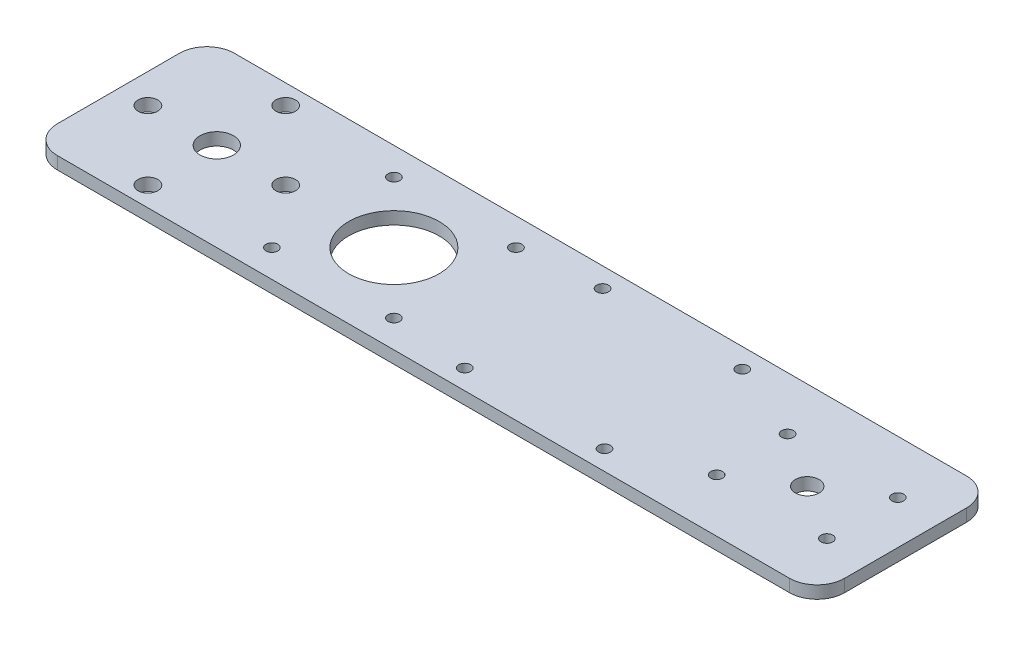
SolidWorks part; units mm, degrees
ref_plane "Front Plane" through (0, 0, 0) normal (0, 0, 1) x (1, 0, 0)
ref_plane "Top Plane" through (0, 0, 0) normal (0, 1, 0) x (1, 0, 0)
ref_plane "Right Plane" through (0, 0, 0) normal (1, 0, 0) x (0, 0, -1)
sketch "Sketch1" plane through (0, 0, 0) normal (0, 1, 0) x (1, 0, 0)
  line L0 (-25, 0) -> (0, 0) construction
  line L1 (-25, 22.5) -> (175, 22.5)
  line L2 (-25, 22.5) -> (-25, -22.5)
  line L3 (-25, -22.5) -> (175, -22.5)
  line L4 (175, 22.5) -> (175, -22.5)
  dimension "D1" = 25
  dimension "D2" = 200
  dimension "D3" = 45
extrude "Boss-Extrude1" add sketch "Sketch1" along normal blind 3.175
sketch "Sketch4" plane through (0, 3.175, 0) normal (0, 1, 0) x (1, 0, 0)
  line L0 (175, 0) -> (-25, 0) construction
  line L1 (175, -22.5) -> (175, 22.5) construction
  line L2 (-25, 22.5) -> (-25, -22.5) construction
  line L3 (150, 22.5) -> (150, -22.5) construction
  line L4 (175, 22.5) -> (-25, 22.5) construction
  line L5 (-25, -22.5) -> (175, -22.5) construction
  circle A0 centre (150, 0) radius 3
  circle A1 centre (136, 9) radius 1.5
  circle A2 centre (164, 9) radius 1.5
  circle A3 centre (164, -9) radius 1.5
  circle A4 centre (136, -9) radius 1.5
  point P8 (0, 0)
  point P14 (0, 0)
  point P15 (0, 0)
  point P16 (150, 27.4454)
  point P24 (0, 0)
  point P29 (0, 0)
  dimension "D1" = 6
  dimension "D5" = 3
  dimension "D2" = 25
  dimension "D3" = 14
  dimension "D4" = 9
extrude "Cut-Extrude1" cut sketch "Sketch4" against normal through all
sketch "Sketch5" plane through (0, 3.175, 0) normal (0, 1, 0) x (1, 0, 0)
  circle A0 centre (0, 0) radius 4.25
  dimension "D1" = 8.5
extrude "Cut-Extrude2" cut sketch "Sketch5" against normal through all
sketch "Sketch6" plane through (0, 3.175, 0) normal (0, 1, 0) x (1, 0, 0)
  line L1 (45, 21) -> (45, -21) construction
  line L2 (24, 0) -> (66, 0) construction
  circle A6 centre (45, 0) radius 11.5
  circle A7 centre (29.5, 15.5) radius 1.5
  circle A8 centre (60.5, 15.5) radius 1.5
  circle A9 centre (60.5, -15.5) radius 1.5
  circle A10 centre (29.5, -15.5) radius 1.5
  point P6 (45, 0)
  point P8 (45, 0)
  dimension "D1" = 23
  dimension "D4" = 3
  dimension "D2" = 45
  dimension "D3" = 42
  dimension "D5" = 15.5
  dimension "D6" = 15.5
extrude "Cut-Extrude3" cut sketch "Sketch6" against normal through all
sketch "Sketch10" plane through (0, 3.175, 0) normal (0, 1, 0) x (1, 0, 0)
  line L0 (-25, 0) -> (175, 0) construction
  line L1 (-25, -22.5) -> (175, -22.5) construction
  line L2 (175, -22.5) -> (175, 22.5) construction
  line L3 (-25, 22.5) -> (-25, -22.5) construction
  circle A0 centre (80.5, -17.5) radius 1.5
  circle A2 centre (116, -17.5) radius 1.5
  circle A3 centre (136, -9) radius 1.5 construction
  circle A4 centre (116, 17.5) radius 1.5
  circle A5 centre (80.5, 17.5) radius 1.5
  circle A6 centre (60.5, -15.5) radius 1.5 construction
  point P11 (0, 0)
  point P21 (0, 0)
  dimension "D3" = 3
  dimension "D4" = 20
  dimension "D1" = 20
  dimension "D2" = 5
extrude "Cut-Extrude4" cut sketch "Sketch10" against normal through all
fillet "Fillet1" radius 7 4 edges at (-25, 1.5875, 22.5) (-25, 1.5875, -22.5) (175, 1.5875, -22.5) (175, 1.5875, 22.5)
sketch "Sketch11" plane through (0, 3.175, 0) normal (0, 1, 0) x (1, 0, 0)
  circle A0 centre (0, 17.5) radius 2.5
  circle A1 centre (17.5, 0) radius 2.5
  circle A2 centre (0, -17.5) radius 2.5
  circle A3 centre (-17.5, 0) radius 2.5
  dimension "D1" = 5
  dimension "D2" = 17.5
  dimension "D3" = 4
extrude "Cut-Extrude5" cut sketch "Sketch11" against normal through all
